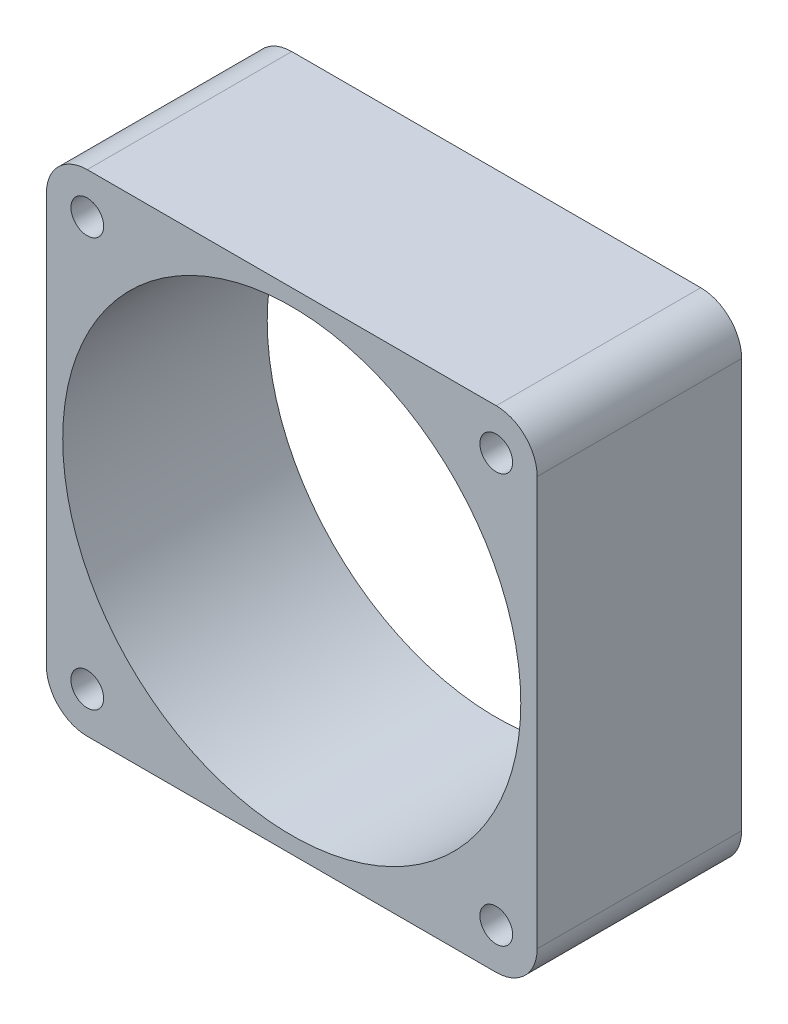
SolidWorks part; units mm, degrees
ref_plane "Plan de face" through (0, 0, 0) normal (0, 0, 1) x (1, 0, 0)
ref_plane "Plan de dessus" through (0, 0, 0) normal (0, 1, 0) x (1, 0, 0)
ref_plane "Plan de droite" through (0, 0, 0) normal (1, 0, 0) x (0, 0, -1)
sketch "Esquisse1" plane through (0, 0, 0) normal (0, 0, 1) x (1, 0, 0)
  line L1 (-60, 60) -> (0, 60)
  line L2 (-60, 60) -> (-60, 0)
  line L3 (-60, 0) -> (0, 0)
  line L4 (0, 60) -> (0, 0)
  dimension "D1" = 60
extrude "Boss.-Extru.1" add sketch "Esquisse1" along normal blind 25
sketch "Esquisse2" plane through (0, 0, 0) normal (0, 0, -1) x (-1, 0, 0)
  line L0 (0, 60) -> (60, 60) construction
  line L1 (0, 0) -> (0, 60) construction
  circle A0 centre (30, 30) radius 28
  point P4 (30, 60)
  point P7 (0, 30)
  dimension "D1" = 56
extrude "Enlèv. mat.-Extru.1" cut sketch "Esquisse2" against normal up to next
sketch "Esquisse3" plane through (0, 0, 0) normal (0, 0, -1) x (-1, 0, 0)
  line L0 (0, 60) -> (60, 60) construction
  line L1 (0, 0) -> (0, 60) construction
  line L2 (60, 60) -> (60, 0) construction
  line L3 (60, 0) -> (0, 0) construction
  circle A0 centre (5, 55) radius 2
  circle A1 centre (55, 55) radius 2
  circle A2 centre (55, 5) radius 2
  circle A3 centre (5, 5) radius 2
  dimension "D1" = 4
  dimension "D2" = 5
  dimension "D3" = 5
  dimension "D4" = 5
  dimension "D5" = 5
extrude "Enlèv. mat.-Extru.2" cut sketch "Esquisse3" against normal blind 25
fillet "Congé1" radius 5 4 edges at (0, 0, 12.5) (-60, 0, 12.5) (-60, 60, 12.5) (0, 60, 12.5)
ref_axis "Axe1" through (-55, 5, 25) along (0, 0, -1)
ref_axis "Axe2" through (-55, 55, 25) along (0, 0, -1)
